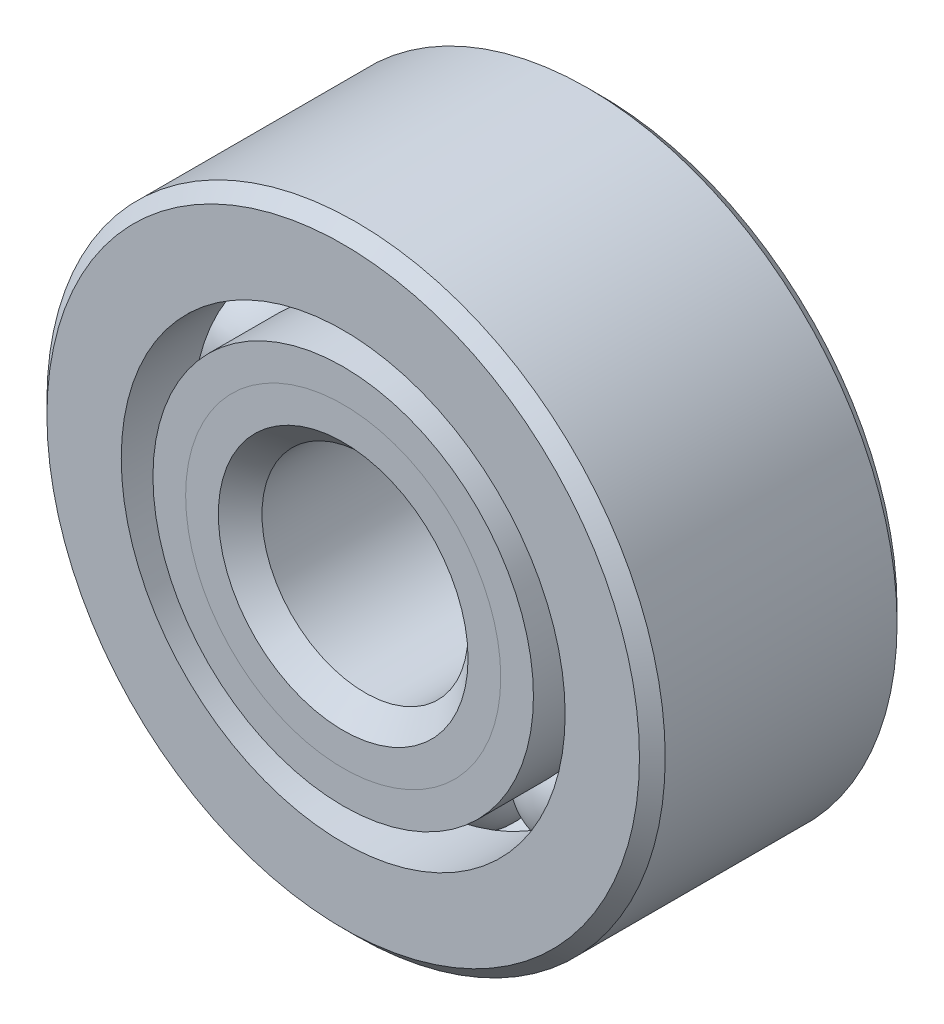
SolidWorks part; units mm, degrees
ref_plane "Front Plane" through (0, 0, 0) normal (0, 0, 1) x (1, 0, 0)
ref_plane "Top Plane" through (0, 0, 0) normal (0, 1, 0) x (1, 0, 0)
ref_plane "Right Plane" through (0, 0, 0) normal (1, 0, 0) x (0, 0, -1)
sketch "Sketch1" plane through (0, 0, 0) normal (1, 0, 0) x (0, 0, -1)
  line L0 (-1.9844, 0) -> (1.9844, 0) construction
  line L1 (0, 4.7625) -> (0, -4.7625) construction
  line L2 (1.7859, 4.7625) -> (-1.7859, 4.7625)
  line L3 (-1.7859, 4.7625) -> (-1.9844, 4.5641)
  line L4 (-1.9844, 4.5641) -> (-1.9844, 3.4192)
  line L5 (-1.9844, 3.4192) -> (-0.8819, 3.4192)
  line L6 (1.9844, 3.4192) -> (0.8819, 3.4192)
  line L7 (1.9844, 4.5641) -> (1.9844, 3.4192)
  line L8 (1.7859, 4.7625) -> (1.9844, 4.5641)
  line L9 (0, 4.7625) -> (0, 3.175) construction
  line L10 (0, 3.175) -> (0, 1.5875) construction
  arc A0 (-0.8819, 3.4192) -> (0.8819, 3.4192) centre (0, 3.175) cw
  point P14 (0, 1.5875)
  dimension "Width" = 3.9688
  dimension "OD" = 9.525
  dimension "D1" = 45
  dimension "D2" = 0.1984
  dimension "D3" = 1.7639
  dimension "D4" = 0.2442
revolve "Revolve1" add sketch "Sketch1" angle 360 about L0
sketch "Sketch2" plane through (0, 0, 0) normal (1, 0, 0) x (0, 0, -1)
  line L0 (-1.9844, 2.9308) -> (-0.8819, 2.9308)
  line L1 (-1.9844, 4.5641) -> (-1.9844, -4.5641) construction
  line L2 (-1.9844, 2.9308) -> (-1.9844, 2.4272)
  line L3 (-1.9844, 2.4272) -> (-1.4808, 1.9237)
  line L4 (-1.4808, 1.9237) -> (0, 1.9237)
  line L5 (0, 4.7625) -> (0, -4.7625) construction
  line L6 (0, 1.9237) -> (0, 2.2599)
  line L7 (0, 2.2599) -> (0, 1.5875) construction
  line L8 (-1.9844, 2.9308) -> (-1.9844, 1.9237) construction
  line L9 (-1.9844, 1.9237) -> (-1.4808, 1.9237) construction
  arc A0 (-0.8819, 2.9308) -> (0, 2.2599) centre (0, 3.175) ccw
  arc A1 (0.8819, 3.4192) -> (-0.8819, 3.4192) centre (0, 3.175) ccw construction
  circle A2 centre (0, 3.175) radius 0.9151 construction
  dimension "D1" = 45
revolve "Revolve2" add sketch "Sketch2" angle 360 about L0
sketch "Sketch3" plane through (0, 0, 0) normal (1, 0, 0) x (0, 0, -1)
  line L0 (-1.9844, 2.4272) -> (-1.4808, 1.9237)
  line L1 (-1.4808, 1.9237) -> (0, 1.9237)
  line L2 (0, 1.9237) -> (0, 2.2599)
  line L3 (-1.9844, 2.4272) -> (-1.9844, 1.9237)
  line L4 (-1.9844, 2.9308) -> (-1.9844, 1.9237) construction
  line L5 (-1.9844, 1.9237) -> (-1.6482, 1.5875)
  line L6 (-1.6482, 1.5875) -> (1.7859, 1.5875)
  line L7 (1.7859, 4.7625) -> (1.7859, -4.7625) construction
  line L8 (1.7859, 1.5875) -> (1.9844, 1.7859)
  line L9 (1.9844, -4.5641) -> (1.9844, 4.5641) construction
  line L10 (1.9844, 1.7859) -> (1.9844, 2.9308)
  line L11 (1.9844, 2.9308) -> (0.8819, 2.9308)
  line L13 (1.7859, 4.7625) -> (1.9844, 4.5641) construction
  circle A0 centre (0, 3.175) radius 0.9151 construction
  arc A1 (0.8819, 2.9308) -> (0, 2.2599) centre (0, 3.175) cw
revolve "Revolve3" add sketch "Sketch3" angle 360 about L0
sketch "Sketch4" plane through (0, 0, 0) normal (1, 0, 0) x (0, 0, -1)
  line L0 (-0.9151, 3.175) -> (0.9151, 3.175)
  circle A1 centre (0, 3.175) radius 0.9151 construction
  arc A2 (-0.9151, 3.175) -> (0.9151, 3.175) centre (0, 3.175) cw
  arc A3 (0.8819, 3.4192) -> (-0.8819, 3.4192) centre (0, 3.175) ccw construction
revolve "Revolve4" add sketch "Sketch4" angle 360 about L0
ref_axis "Axis1" through (0, 0, -1.9844) along (0, 0, 1)
pattern_circular "CirPattern1" count 10 every 36 about axis through (0, 0, -1.9844) along (0, 0, 1) of bodies 104
equation "\"D2@Sketch1\" = \"Width@Sketch1\"*.05"
equation "\"D3@Sketch1\" = \"Width@Sketch1\"/2.25"
equation "\"D4@Sketch1\" = (((\"OD@Sketch1\"-\"Width@Sketch1\")/2)/3.25)/3.5"
equation "\"D2@CirPattern1\" = 360/\"Balls@CirPattern1\""
